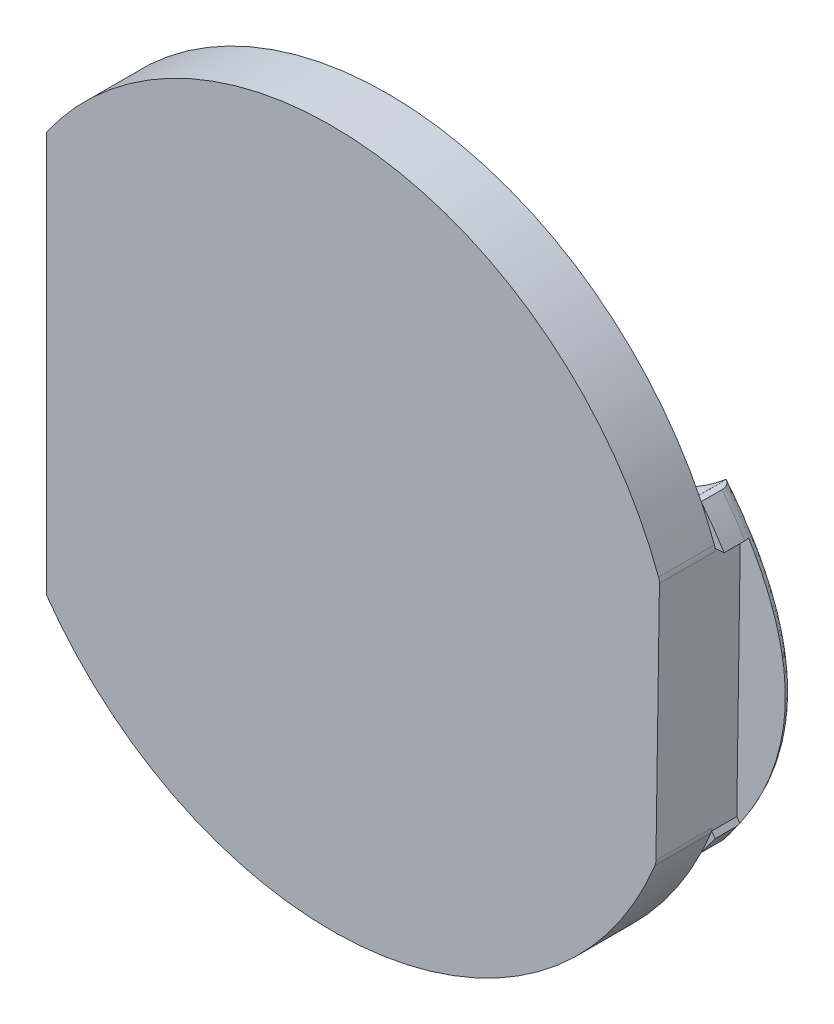
SolidWorks part; units mm, degrees
ref_plane "Front Plane" through (0, 0, 0) normal (0, 0, 1) x (1, 0, 0)
ref_plane "Top Plane" through (0, 0, 0) normal (0, 1, 0) x (1, 0, 0)
ref_plane "Right Plane" through (0, 0, 0) normal (1, 0, 0) x (0, 0, -1)
sketch "Sketch1" plane through (0, 0, 0) normal (0, 0, 1) x (1, 0, 0)
  line L0 (-12.5, 0) -> (0, 0) construction
  line L1 (-10.23, -1000) -> (-10.23, 49000) construction
  line L2 (-10.23, 7.1831) -> (-10.23, -7.1831)
  arc A0 (-10.23, -7.1831) -> (-10.23, 7.1831) centre (0, 0) ccw
  point P5 (-10.23, 0)
  dimension "D1" = 25
  dimension "D2" = 2.27
extrude "Boss-Extrude1" add sketch "Sketch1" along normal blind 2
sketch "Sketch2" plane through (0, 0, 0) normal (0, 0, -1) x (-1, 0, 0)
  line L0 (10.23, 7.1831) -> (10.23, -7.1831) construction
  line L1 (8.73, 0.6772) -> (10.23, 0.6772)
  line L2 (8.73, 0.6772) -> (8.73, -0.8228)
  line L3 (8.73, -0.8228) -> (10.23, -0.8228)
  line L4 (10.23, 0.6772) -> (10.23, -0.8228)
  line L5 (8.73, 0.6772) -> (10.23, -0.8228) construction
  line L6 (8.73, -0.8228) -> (10.23, 0.6772) construction
  point P0 (9.48, -0.0728)
  dimension "D1" = 1.5
  dimension "D2" = 1.5
extrude "Boss-Extrude3" add sketch "Sketch2" along normal blind 1.5
sketch "Sketch3" plane through (-10.23, 0, 0) normal (-1, 0, 0) x (0, 0, 1)
  line L0 (-1.5, -0.8228) -> (0, -0.8228) construction
  line L1 (-1.5, 0.6772) -> (-0.5019, 0.6772)
  line L2 (-1.5, 0.6772) -> (-1.5, -0.8228)
  line L3 (-1.5, -0.8228) -> (-0.5019, -0.8228)
  line L4 (-0.5019, 0.6772) -> (-0.5019, -0.8228)
extrude "Boss-Extrude4" add sketch "Sketch3" along normal blind 1.25
sketch "Sketch4" plane through (0, -0.8228, 0) normal (0, -1, 0) x (1, 0, 0)
  line L0 (-11.48, -0.5019) -> (-11.48, -1.0009) construction
  line L1 (-11.48, -1.5) -> (-11.48, -0.5019) construction
  line L2 (-11.48, -1.0009) -> (-10.98, -1.0009) construction
  circle A0 centre (-10.98, -1.0009) radius 0.5
  dimension "D1" = 0.5
extrude "Boss-Extrude5" add sketch "Sketch4" along normal blind 1.25 and the other way blind 2.75
sketch "Sketch6" plane through (0, 0, 0) normal (0, 0, -1) x (-1, 0, 0)
  line L0 (0, 0) -> (-12.5, 0) construction
  line L1 (-11.25, -1000) -> (-11.25, 49000) construction
  line L3 (-11.25, -5.4486) -> (-11.0113, -5.4486)
  line L4 (-11.0113, -5.4486) -> (-11.0113, 5.4486)
  line L5 (-11.0113, 5.4486) -> (-11.25, 5.4486)
  arc A0 (10.23, 7.1831) -> (10.23, -7.1831) centre (0, 0) ccw construction
  spline S0 degree 2 poles (-11.25, 5.4486) (-15.5341, 0) (-11.25, -5.4486) knots 0 0 0 1 1 1
  dimension "D1" = 1.25
extrude "Boss-Extrude6" add sketch "Sketch6" along normal blind 1.25
sketch "Sketch7" plane through (0, -5.4486, 0) normal (0, -1, 0) x (1, 0, 0)
  line L0 (-10.23, 0) -> (11.25, 0) construction
  line L1 (10.3107, 0) -> (11.0113, 0)
  line L2 (11.0113, 0) -> (11.0113, -1.25)
  spline S0 degree 2 poles (11.0113, -1.25) (10.9405, -0.4772) (10.3107, 0) knots 0 0 0 1 1 1
extrude "Boss-Extrude7" add sketch "Sketch7" against normal blind 10.9
sketch "Sketch8" plane through (0, 0, 0) normal (0, 0, 1) x (1, 0, 0)
  line L0 (11.7545, 4.2522) -> (11.6258, -4.5924)
  line L1 (11.6258, -4.5924) -> (11.7545, -4.764)
  arc A0 (-10.23, -7.1831) -> (-10.23, 7.1831) centre (0, 0) ccw construction
  parabola Q0 (11.25, 5.4486) -> (11.25, -5.4486) focus (9.9272, 0) apex (13.3921, 0) construction
  parabola Q3 (11.25, 5.4486) -> (11.25, -5.4486) focus (9.9272, 0) apex (13.3921, 0) construction
  parabola Q9 (11.25, 5.4486) -> (11.25, -5.4486) focus (9.9272, 0) apex (13.3921, 0) construction
  parabola Q11 (11.25, 5.4486) -> (11.25, -5.4486) focus (9.9272, 0) apex (13.3921, 0) construction
  spline S0 degree 1 poles (11.7545, 4.2522) (12.074, 4.2741) knots 0 0 1 1
  spline S1 degree 2 poles (12.074, 4.2741) (13.0719, 2.8185) (13.2947, 1.1619) knots 0 0 0 1 1 1
  spline S2 degree 2 poles (13.0464, -2.1887) (13.4027, -3.939) (11.7545, -4.764) knots 0 0 0 1 1 1
  spline S3 degree 2 poles (13.2947, 1.1619) (14.2951, -0.5582) (13.0464, -2.1887) knots 0 0 0 1 1 1
extrude "Cut-Extrude5" cut sketch "Sketch8" against normal blind 0.9 and the other way blind 12.9
fillet "Fillet2" radius 0.5 3 edges at (11.6258, -4.5924, 1) (11.7545, 4.2522, 1)
